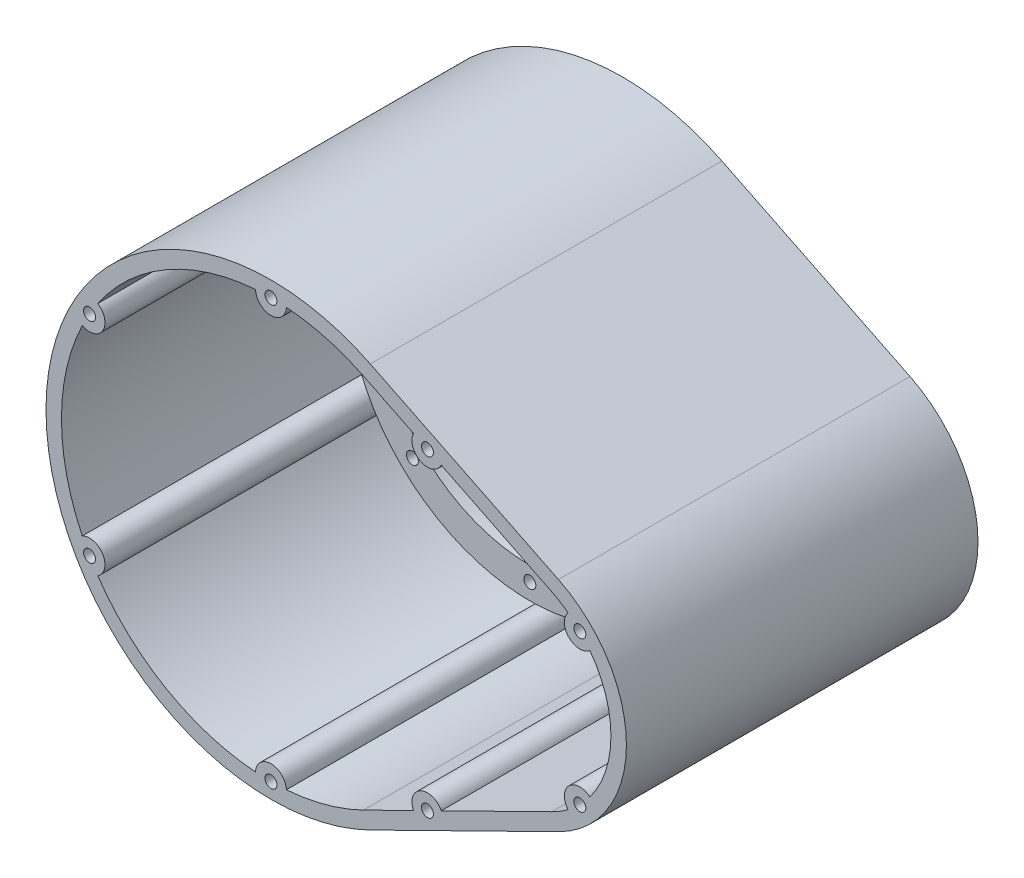
SolidWorks part; units mm, degrees
ref_plane "Front Plane" through (0, 0, 0) normal (0, 0, 1) x (1, 0, 0)
ref_plane "Top Plane" through (0, 0, 0) normal (0, 1, 0) x (1, 0, 0)
ref_plane "Right Plane" through (0, 0, 0) normal (1, 0, 0) x (0, 0, -1)
sketch "Sketch1" plane through (0, 0, 0) normal (0, 0, 1) x (1, 0, 0)
  line L0 (74.4125, 28.2611) -> (25.7142, 52.2345)
  line L1 (0, 0) -> (60.5, 0) construction
  line L5 (74.4125, -28.2611) -> (25.7142, -52.2345)
  circle A1 centre (0, 0) radius 58.2208 construction
  circle A11 centre (60.5, 0) radius 31.5 construction
  arc A12 (25.7142, 52.2345) -> (25.7142, -52.2345) centre (0, 0) ccw
  arc A13 (74.4125, 28.2611) -> (74.4125, -28.2611) centre (60.5, 0) cw
  point P22 (0, 0)
extrude "Boss-Extrude2" add sketch "Sketch1" along normal blind 8
sketch "Sketch5" plane through (0, 0, 8) normal (0, 0, 1) x (1, 0, 0)
  line L0 (20.8559, 42.3656) -> (69.5542, 18.3922)
  line L1 (69.5542, -18.3922) -> (20.8559, -42.3656)
  line L2 (17.3225, 35.1881) -> (66.0208, 11.2147)
  line L3 (17.3225, -35.1881) -> (66.0208, -11.2147)
  line L4 (0, 0) -> (60.5, 0) construction
  circle A0 centre (0, 0) radius 43.2208 construction
  circle A1 centre (60.5, 0) radius 16.5 construction
  circle A4 centre (60.5, 0) radius 12.5 construction
  circle A5 centre (60.5, 0) radius 20.5 construction
  circle A6 centre (0, 0) radius 39.2208 construction
  circle A7 centre (0, 0) radius 47.2208 construction
  arc A8 (20.8559, 42.3656) -> (20.8559, -42.3656) centre (0, 0) ccw
  arc A9 (17.3225, 35.1881) -> (17.3225, -35.1881) centre (0, 0) ccw
  arc A10 (66.0208, 11.2147) -> (66.0208, -11.2147) centre (60.5, 0) cw
  arc A11 (69.5542, 18.3922) -> (69.5542, -18.3922) centre (60.5, 0) cw
  point P22 (0, 0)
extrude "Boss-Extrude3" add sketch "Sketch5" along normal blind 16
sketch "Sketch6" plane through (0, 0, 24) normal (0, 0, 1) x (1, 0, 0)
  line L0 (0, 0) -> (0, 43) construction
  line L1 (60.5, 0) -> (77, 0) construction
  line L2 (20.8559, 42.3656) -> (69.5542, 18.3922) construction
  line L3 (20.8559, -42.3656) -> (69.5542, -18.3922) construction
  line L4 (20.8559, 42.3656) -> (34.716, 35.5424) construction
  line L5 (34.716, 35.5424) -> (32.9494, 31.9537) construction
  line L6 (69.5542, 18.3922) -> (60.5824, 22.8088) construction
  line L7 (60.5824, 22.8088) -> (58.8157, 19.2201) construction
  line L8 (20.8559, -42.3656) -> (34.716, -35.5424) construction
  line L9 (34.716, -35.5424) -> (32.9494, -31.9537) construction
  line L10 (69.5542, -18.3922) -> (60.5824, -22.8088) construction
  line L11 (60.5824, -22.8088) -> (58.8157, -19.2201) construction
  line L12 (0, 0) -> (60.5, 0) construction
  circle A0 centre (0, 43) radius 1.55
  circle A1 centre (60.5, 0) radius 16.5 construction
  circle A8 centre (77, 0) radius 1.55
  circle A9 centre (0, 0) radius 47.2208 construction
  circle A10 centre (60.5, 0) radius 20.5 construction
  arc A11 (69.5542, 18.3922) -> (69.5542, -18.3922) centre (60.5, 0) cw construction
  arc A12 (20.8559, 42.3656) -> (20.8559, -42.3656) centre (0, 0) ccw construction
  circle A13 centre (58.8157, 19.2201) radius 1.55
  circle A14 centre (32.9494, 31.9537) radius 1.55
  circle A15 centre (58.8157, -19.2201) radius 1.55
  circle A16 centre (32.9494, -31.9537) radius 1.55
  circle A17 centre (-30.4056, 30.4056) radius 1.55
  circle A18 centre (-43, 0) radius 1.55
  circle A19 centre (-30.4056, -30.4056) radius 1.55
  circle A20 centre (0, -43) radius 1.55
  point P21 (0.2659, 0.1121)
  point P41 (0, 0)
  dimension "D1" = 5
extrude "Cut-Extrude1" cut sketch "Sketch6" against normal up to surface (24 mm away) up to face at (33.4765, 0, 0)
sketch "Sketch7" plane through (0, 0, 8) normal (0, 0, 1) x (1, 0, 0)
  circle A0 centre (0, 0) radius 8.2
extrude "Cut-Extrude2" cut sketch "Sketch7" against normal blind 5 contours A0
sketch "Sketch8" plane through (0, 0, 8) normal (0, 0, 1) x (1, 0, 0)
  circle A0 centre (60.5, 0) radius 2
extrude "Boss-Extrude4" add sketch "Sketch8" along normal blind 8.5
sketch "Sketch9" plane through (0, 0, 0) normal (0, 0, -1) x (-1, 0, 0)
  line L0 (-77, 0) -> (0, 0) construction
  circle A10 centre (-77, 0) radius 3.5
  circle A11 centre (-58.8157, 19.2201) radius 3.5
  circle A12 centre (-32.9494, 31.9537) radius 3.5
  circle A13 centre (0, 43) radius 3.5
  circle A14 centre (30.4056, 30.4056) radius 3.5
  circle A15 centre (30.4056, -30.4056) radius 3.5
  circle A16 centre (0, -43) radius 3.5
  circle A17 centre (-32.9494, -31.9537) radius 3.5
  circle A18 centre (-58.8157, -19.2201) radius 3.5
  circle A19 centre (43, 0) radius 3.5
extrude "Cut-Extrude3" cut sketch "Sketch9" against normal blind 3
sketch "Sketch10" plane through (0, 0, 8) normal (0, 0, 1) x (1, 0, 0)
  line L1 (25.7142, 52.2345) -> (74.4125, 28.2611)
  line L3 (25.7142, -52.2345) -> (74.4125, -28.2611)
  line L6 (22.1809, 45.0571) -> (70.8792, 21.0837) construction
  line L7 (22.1809, -45.0571) -> (70.8792, -21.0837) construction
  line L8 (23.9475, 48.6458) -> (36.9095, 42.2649)
  line L9 (23.9475, -48.6458) -> (36.9095, -42.2649)
  line L10 (0, 0) -> (0, 54.2208) construction
  line L11 (0, 0) -> (40.4982, 40.4982) construction
  line L12 (60.5, 0) -> (79.9454, -19.4454) construction
  line L13 (60.5, 0) -> (79.9454, 19.4454) construction
  line L16 (0, 0) -> (58.5, 0) construction
  line L17 (0, 0) -> (40.4982, -40.4982) construction
  line L18 (44.0869, -38.7315) -> (72.6458, -24.6724)
  line L19 (44.0869, 38.7315) -> (72.6458, 24.6724)
  arc A33 (74.4125, 28.2611) -> (74.4125, -28.2611) centre (60.5, 0) cw
  arc A34 (25.7142, 52.2345) -> (25.7142, -52.2345) centre (0, 0) ccw
  arc A37 (70.8792, 21.0837) -> (70.8792, -21.0837) centre (60.5, 0) cw construction
  arc A38 (22.1809, 45.0571) -> (22.1809, -45.0571) centre (0, 0) ccw construction
  circle A47 centre (60.5, 0) radius 2 construction
  circle A48 centre (60.5, 0) radius 2 construction
  arc A51 (-48.8275, 23.5749) -> (-44.8302, 30.4984) centre (-46.9566, 27.1104) ccw
  arc A52 (-3.9973, 54.0733) -> (3.9973, 54.0733) centre (0, 54.2208) ccw
  arc A53 (36.9095, 42.2649) -> (44.0869, 38.7315) centre (40.4982, 40.4982) ccw
  arc A54 (76.9188, 22.0607) -> (82.5607, 16.4188) centre (79.9454, 19.4454) ccw
  arc A55 (76.9188, -22.0607) -> (82.5607, -16.4188) centre (79.9454, -19.4454) cw
  arc A56 (36.9095, -42.2649) -> (44.0869, -38.7315) centre (40.4982, -40.4982) cw
  arc A57 (-3.9973, -54.0733) -> (3.9973, -54.0733) centre (0, -54.2208) cw
  arc A58 (-48.8275, -23.5749) -> (-44.8302, -30.4984) centre (-46.9566, -27.1104) cw
  arc A59 (72.6458, 24.6724) -> (76.9188, 22.0607) centre (60.5, 0) cw
  arc A60 (23.9475, 48.6458) -> (3.9973, 54.0733) centre (0, 0) ccw
  arc A61 (-3.9973, 54.0733) -> (-44.8302, 30.4984) centre (0, 0) ccw
  arc A62 (-48.8275, 23.5749) -> (-48.8275, -23.5749) centre (0, 0) ccw
  arc A63 (3.9973, -54.0733) -> (23.9475, -48.6458) centre (0, 0) ccw
  arc A64 (-44.8302, -30.4984) -> (-3.9973, -54.0733) centre (0, 0) ccw
  arc A65 (76.9188, -22.0607) -> (72.6458, -24.6724) centre (60.5, 0) cw
  arc A66 (82.5607, 16.4188) -> (82.5607, -16.4188) centre (60.5, 0) cw
  point P4 (0, 0)
  point P28 (0, 0)
extrude "Boss-Extrude5" add sketch "Sketch10" along normal blind 83
sketch "Sketch11" plane through (0, 0, 91) normal (0, 0, 1) x (1, 0, 0)
  line L0 (0, 0) -> (60.5, 0) construction
  line L1 (23.9475, 48.6458) -> (72.6458, 24.6724) construction
  line L2 (23.9475, -48.6458) -> (72.6458, -24.6724) construction
  line L3 (44.0869, -38.7315) -> (72.6458, -24.6724) construction
  line L4 (0, 0) -> (40.4982, 40.4982) construction
  line L5 (60.5, 0) -> (79.9454, 19.4454) construction
  circle A15 centre (60.5, 0) radius 27.5 construction
  circle A16 centre (0, 0) radius 54.2208 construction
  circle A17 centre (0, 54.2208) radius 1.55
  circle A18 centre (-46.9566, 27.1104) radius 1.55
  circle A19 centre (-46.9566, -27.1104) radius 1.55
  circle A20 centre (0, -54.2208) radius 1.55
  circle A21 centre (79.9454, 19.4454) radius 1.55
  circle A23 centre (40.4982, 40.4982) radius 1.55
  circle A24 centre (79.9454, -19.4454) radius 1.55
  circle A25 centre (40.4982, -40.4982) radius 1.55
  point P22 (0, 0)
extrude "Cut-Extrude4" cut sketch "Sketch11" against normal blind 10 and the other way through all
